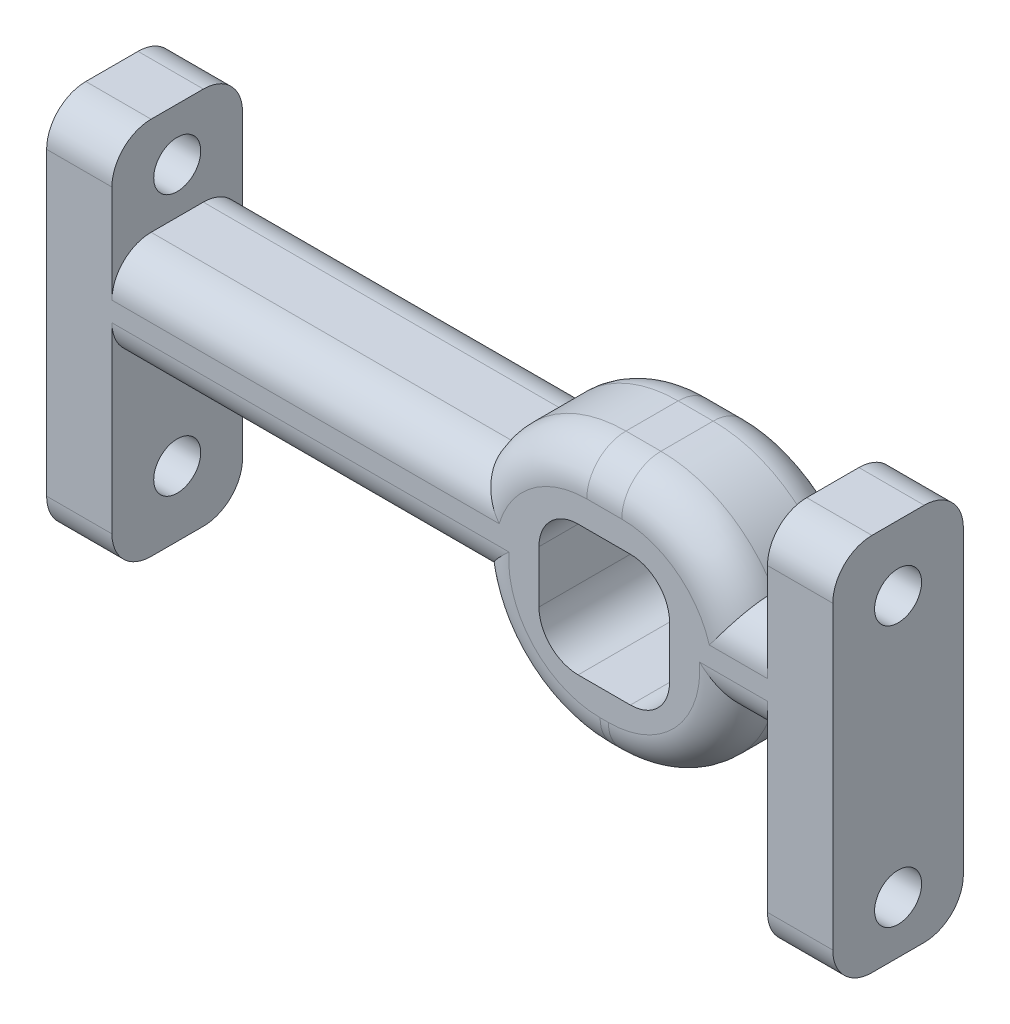
SolidWorks part; units mm, degrees
ref_plane "Plan de face" through (0, 0, 0) normal (0, 0, 1) x (1, 0, 0)
ref_plane "Plan de dessus" through (0, 0, 0) normal (0, 1, 0) x (1, 0, 0)
ref_plane "Plan de droite" through (0, 0, 0) normal (1, 0, 0) x (0, 0, -1)
sketch "Esquisse1" plane through (0, 0, 0) normal (0, 0, 1) x (1, 0, 0)
  line L0 (0, 29) -> (0, 0)
  line L1 (0, 29) -> (5, 29)
  line L2 (0, 0) -> (5, 0)
  line L3 (5, 29) -> (5, 0)
  line L4 (60.2, 29) -> (55.2, 29)
  line L5 (60.2, 29) -> (60.2, 0)
  line L6 (55.2, 29) -> (55.2, 0)
  line L7 (60.2, 0) -> (55.2, 0)
  line L8 (5, 21.5) -> (55.2, 21.5)
  line L9 (5, 21.5) -> (5, 14)
  line L10 (55.2, 21.5) -> (55.2, 14)
  line L11 (5, 14) -> (55.2, 14)
  line L12 (32.7, 26.5) -> (32.7, 6.5)
  line L13 (32.7, 26.5) -> (52.7, 26.5)
  line L14 (32.7, 6.5) -> (52.7, 6.5)
  line L15 (52.7, 26.5) -> (52.7, 6.5)
  line L16 (37.7, 21.5) -> (37.7, 11.5)
  line L17 (37.7, 21.5) -> (47.7, 21.5)
  line L18 (37.7, 11.5) -> (47.7, 11.5)
  line L19 (47.7, 21.5) -> (47.7, 11.5)
  dimension "D1" = 7.5
  dimension "D2" = 29
  dimension "D3" = 7.5
  dimension "D4" = 5
  dimension "D5" = 5
  dimension "D6" = 10
  dimension "D7" = 10
  dimension "D8" = 20
  dimension "D9" = 20
  dimension "D10" = 5
  dimension "D11" = 5
  dimension "D12" = 2.5
  dimension "D13" = 60.2
extrude "Boss.-Extru.1" add sketch "Esquisse1" along normal blind 10 contours L15 L13 L12 L8 | L8 L19 L11 L15 | L15 L11 L12 L14 | L16 L8 L12 L11 | L12 L8 L3 L11 | L8 L15 L11 L6 | L7 L5 L4 L6 | L3 L1 L0 L2 region at (2.5, 14.5, 0) region at (18.85, 17.75, 0) region at (42.7, 24, 0) region at (35.2, 17.75, 0) region at (42.7, 9.75, 0) region at (50.2, 17.75, 0) region at (53.95, 17.75, 0) region at (57.7, 14.5, 0)
fillet "Congé1" radius 10 4 edges at (52.7, 6.5, 5) (32.7, 6.5, 5) (52.7, 26.5, 5) (32.7, 26.5, 5)
fillet "Congé2" radius 3 4 edges at (37.7, 11.5, 5) (47.7, 11.5, 5) (47.7, 21.5, 5) (37.7, 21.5, 5)
sketch "Esquisse2" plane through (60.2, 0, 0) normal (1, 0, 0) x (0, 0, -1)
  line L0 (0, 29) -> (0, 0) construction
  line L1 (-10, 29) -> (0, 29) construction
  circle A0 centre (-5, 24) radius 1.8
  circle A1 centre (-5, 4) radius 1.8
  dimension "D1" = 3.6
  dimension "D2" = 5
  dimension "D3" = 3.6
  dimension "D4" = 5
  dimension "D5" = 20
  dimension "D6" = 5
extrude "Enlèv. mat.-Extru.1" cut sketch "Esquisse2" against normal blind 5
sketch "Esquisse3" plane through (0, 0, 0) normal (-1, 0, 0) x (0, 0, 1)
  line L0 (10, 29) -> (10, 0) construction
  line L1 (10, 0) -> (0, 0) construction
  circle A0 centre (5, 25) radius 1.8
  circle A1 centre (5, 5) radius 1.8
  dimension "D1" = 3.6
  dimension "D2" = 3.6
  dimension "D3" = 5
  dimension "D4" = 5
  dimension "D5" = 20
  dimension "D6" = 5
extrude "Enlèv. mat.-Extru.2" cut sketch "Esquisse3" against normal blind 10
fillet "Congé3" radius 3 28 edges at (49.1413, 8.5943, 10) (42.7, 6.5, 10) (49.1413, 8.5943, 0) (42.7, 6.5, 0) (36.3603, 25.1603, 0) (49.0397, 25.1603, 0) (36.2587, 8.5943, 10) (18.85, 14, 10) (18.85, 21.5, 10) (53.95, 21.5, 0) (53.95, 14, 0) (36.2587, 8.5943, 0) (42.7, 26.5, 0) (18.85, 14, 0) (18.85, 21.5, 0) (2.5, 29, 10) (2.5, 29, 0) (57.7, 29, 0) (57.7, 29, 10) (57.7, 0, 0) (57.7, 0, 10) (2.5, 0, 0) (2.5, 0, 10) (36.3603, 25.1603, 10) (49.0397, 25.1603, 10) (42.7, 26.5, 10) (53.95, 14, 10) (53.95, 21.5, 10)
